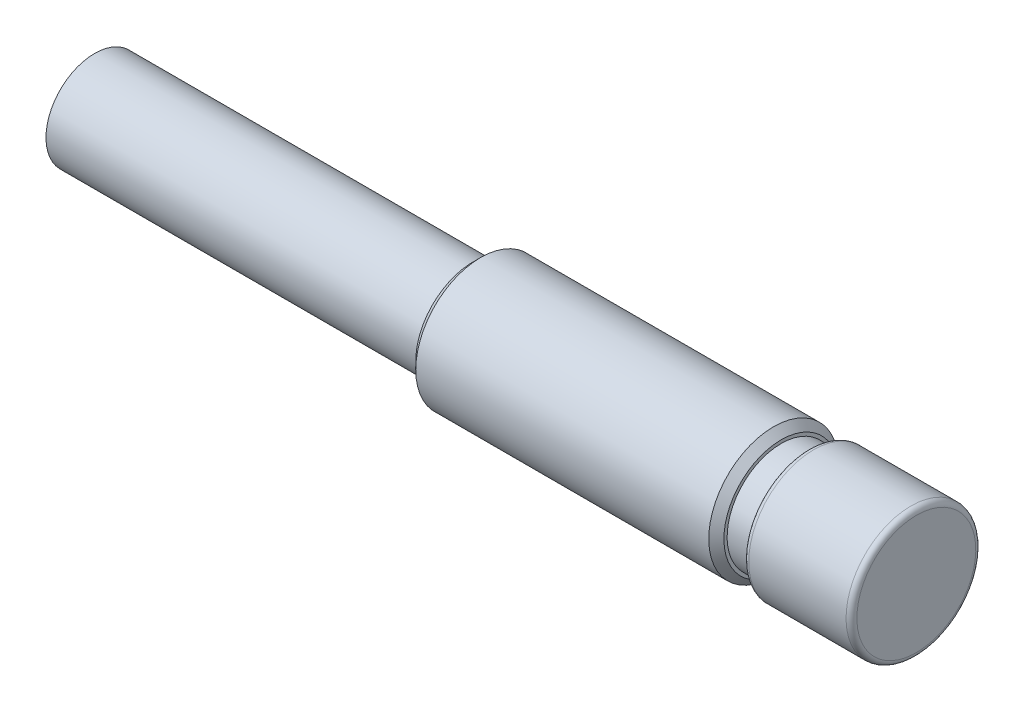
SolidWorks part; units mm, degrees
ref_plane "Plano frontal" through (0, 0, 0) normal (0, 0, 1) x (1, 0, 0)
ref_plane "Plano superior" through (0, 0, 0) normal (0, 1, 0) x (1, 0, 0)
ref_plane "Plano direito" through (0, 0, 0) normal (1, 0, 0) x (0, 0, -1)
sketch "Esboço1" plane through (0, 0, 0) normal (0, 0, 1) x (1, 0, 0)
  line L0 (0, 0) -> (0, 4.5)
  line L1 (0, 4.5) -> (35, 4.5)
  line L2 (35, 4.5) -> (35, 6)
  line L3 (35, 6) -> (63.5, 6)
  line L4 (63.5, 6) -> (63.5, 5)
  line L5 (63.5, 5) -> (66, 5)
  line L6 (66, 5) -> (66, 6)
  line L7 (66, 6) -> (76, 6)
  line L8 (76, 6) -> (76, 0)
  line L9 (76, 0) -> (0, 0)
  point P6 (49.25, 6)
  point P12 (71, 6)
  point P13 (63.5, 5.5)
  point P14 (66, 5.5)
  dimension "D1" = 4.5
  dimension "D2" = 6
  dimension "D3" = 35
  dimension "D4" = 10
  dimension "D5" = 2.5
  dimension "D6" = 76
  dimension "D7" = 1
revolve "Revolução1" add sketch "Esboço1" angle 360 about L9
cosmetic thread "Representação de rosca1" parameters "D2"=10.072
chamfer "Chanfro1" distance 0.7 angle 45 2 edges at (63.5, 6, 0) (35, 6, 0)
fillet "Filete1" radius 0.5 2 edges at (76, 6, 0) (66, 6, 0)
sketch "Esboço5" plane through (0, 0, 0) normal (-1, 0, 0) x (0, 0, 1)
  circle A0 centre (0, 0) radius 1.4
  dimension "D1" = 2.8
extrude "Corte-extrusão1" cut sketch "Esboço5" against normal blind 3
chamfer "Chanfro3" distance 2.8 angle 45 1 edges at (0, -1.4, 0)
fillet "Filete2" radius 4 1 edges at (3, -1.4, 0)
